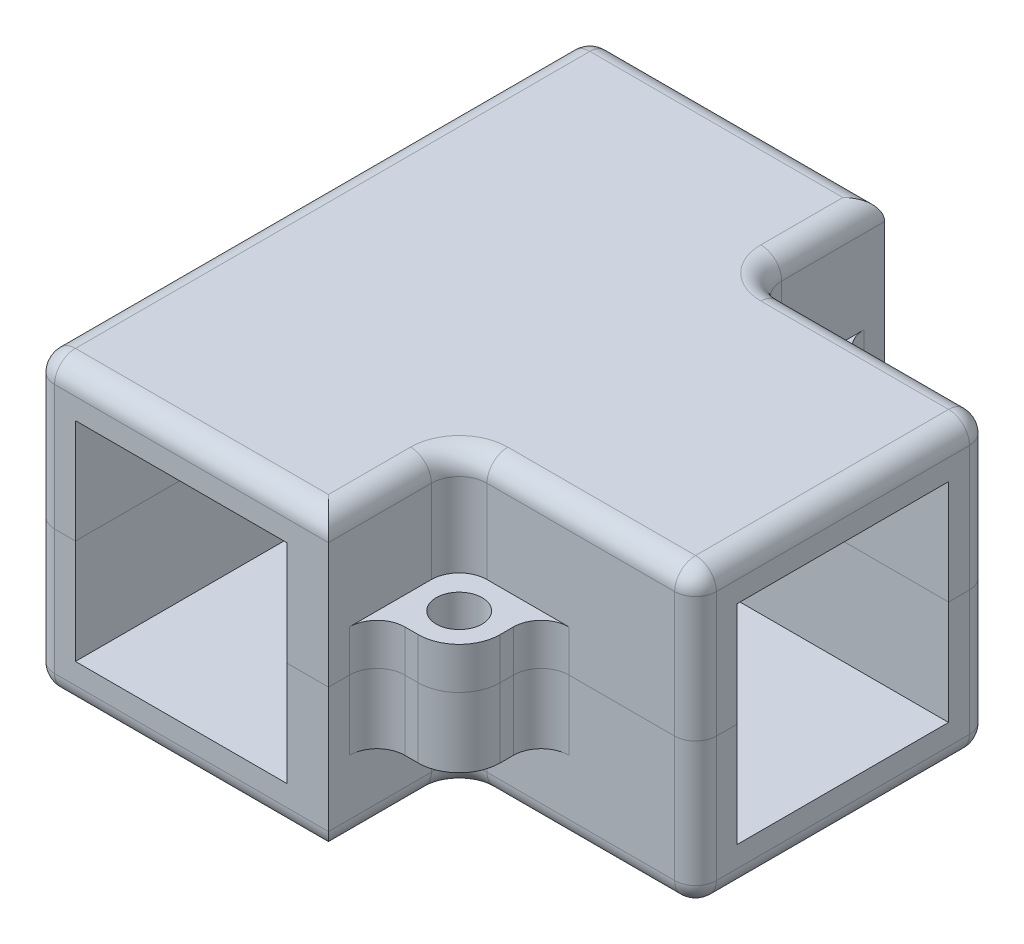
SolidWorks part; units mm, degrees
ref_plane "Front Plane" through (0, 0, 0) normal (0, 0, 1) x (1, 0, 0)
ref_plane "Top Plane" through (0, 0, 0) normal (0, 1, 0) x (1, 0, 0)
ref_plane "Right Plane" through (0, 0, 0) normal (1, 0, 0) x (0, 0, -1)
sketch "Sketch1" plane through (0, 0, 0) normal (0, 1, 0) x (1, 0, 0)
  line L0 (15.2, 20) -> (35.2, 20) construction
  line L1 (0, 0) -> (15.2, 0)
  line L2 (0, 0) -> (0, 40)
  line L3 (0, 40) -> (15.2, 40)
  line L4 (15.2, 0) -> (15.2, 40)
  line L6 (15.2, 12.4) -> (35.2, 12.4)
  line L7 (15.2, 12.4) -> (15.2, 27.6)
  line L8 (15.2, 27.6) -> (35.2, 27.6)
  line L9 (35.2, 12.4) -> (35.2, 27.6)
  line L10 (15.2, 12.4) -> (35.2, 27.6) construction
  line L11 (15.2, 27.6) -> (35.2, 12.4) construction
  point P7 (25.2, 20)
  dimension "D1" = 15.2
  dimension "D2" = 15.2
  dimension "D3" = 40
  dimension "D4" = 20
sketch "Sketch3" plane through (0, 0, 0) normal (0, 1, 0) x (1, 0, 0)
  line L0 (35.2, 27.6) -> (15.2, 27.6)
  line L1 (15.2, 27.6) -> (15.2, 40)
  line L2 (15.2, 40) -> (18.2, 40)
  line L3 (18.2, 40) -> (18.2, 30.6)
  line L4 (18.2, 30.6) -> (35.2, 30.6)
  line L5 (35.2, 30.6) -> (35.2, 27.6)
  line L6 (0, 20) -> (35.2, 20) construction
  line L7 (0, 0) -> (0, 40) construction
  line L8 (18.2, 9.4) -> (35.2, 9.4)
  line L9 (18.2, 0) -> (18.2, 9.4)
  line L10 (15.2, 0) -> (18.2, 0)
  line L11 (15.2, 12.4) -> (15.2, 0)
  line L12 (35.2, 12.4) -> (15.2, 12.4)
  line L13 (35.2, 9.4) -> (35.2, 12.4)
  line L15 (0, 40) -> (-3, 40)
  line L16 (0, 40) -> (0, 0)
  line L17 (0, 0) -> (-3, 0)
  line L18 (-3, 40) -> (-3, 0)
  dimension "D1" = 3
extrude "Boss-Extrude1" add sketch "Sketch3" along normal blind 7.5
sketch "Sketch4" plane through (0, 7.5, 0) normal (0, 1, 0) x (1, 0, 0)
  line L0 (-3, 40) -> (-3, 0)
  line L1 (-3, 0) -> (18.2, 0)
  line L2 (18.2, 0) -> (18.2, 9.4)
  line L3 (18.2, 9.4) -> (35.2, 9.4)
  line L4 (35.2, 9.4) -> (35.2, 30.6)
  line L5 (35.2, 30.6) -> (18.2, 30.6)
  line L6 (18.2, 30.6) -> (18.2, 40)
  line L7 (18.2, 40) -> (-3, 40)
extrude "Boss-Extrude2" add sketch "Sketch4" along normal blind 3
sketch "Sketch5" plane through (0, 0, 0) normal (0, 1, 0) x (1, 0, 0)
  line L0 (18.2, 30.6) -> (18.2, 40) construction
  line L1 (35.2, 30.6) -> (18.2, 30.6) construction
  line L4 (21.15, 36.5) -> (18.2, 36.5)
  line L5 (18.2, 36.5) -> (18.2, 30.6)
  line L6 (18.2, 30.6) -> (24.1, 30.6)
  line L7 (24.1, 30.6) -> (24.1, 33.55)
  line L8 (35.2, 20) -> (-3, 20) construction
  line L9 (35.2, 9.4) -> (35.2, 30.6) construction
  line L10 (-3, 40) -> (-3, 0) construction
  line L11 (24.1, 9.4) -> (24.1, 6.45)
  line L12 (18.2, 9.4) -> (24.1, 9.4)
  line L13 (18.2, 3.5) -> (18.2, 9.4)
  line L14 (21.15, 3.5) -> (18.2, 3.5)
  line L15 (-5.95, 22.95) -> (-3, 22.95)
  line L16 (-3, 22.95) -> (-3, 17.05)
  line L17 (-3, 17.05) -> (-5.95, 17.05)
  circle A0 centre (21.15, 33.55) radius 1.65
  circle A2 centre (21.15, 33.55) radius 2.95 construction
  arc A4 (24.1, 33.55) -> (21.15, 36.5) centre (21.15, 33.55) ccw
  circle A5 centre (21.15, 6.45) radius 2.95 construction
  arc A6 (24.1, 6.45) -> (21.15, 3.5) centre (21.15, 6.45) cw
  circle A7 centre (21.15, 6.45) radius 1.65
  circle A8 centre (-5.95, 20) radius 2.95 construction
  circle A9 centre (-5.95, 20) radius 1.65
  arc A10 (-5.95, 17.05) -> (-5.95, 22.95) centre (-5.95, 20) cw
  dimension "D1" = 3.3
  dimension "D2" = 5.9
  dimension "D3" = 5.9
  dimension "D4" = 3.3
extrude "Boss-Extrude3" add sketch "Sketch5" along normal blind 3
fillet "Fillet1" radius 2 2 edges at (18.2, 6.75, -9.4) (18.2, 6.75, -30.6)
fillet "Fillet2" radius 2 6 edges at (18.2, 1.5, -3.5) (24.1, 1.5, -9.4) (24.1, 1.5, -30.6) (18.2, 1.5, -36.5) (-3, 1.5, -22.95) (-3, 1.5, -17.05)
fillet "Fillet3" radius 1.5 14 edges at (18.2, 10.5, -36.3) (18.7858, 10.5, -31.1858) (27.7, 10.5, -30.6) (35.2, 10.5, -20) (27.7, 10.5, -9.4) (18.7858, 10.5, -8.8142) (18.2, 10.5, -3.7) (7.6, 10.5, 0) (-3, 10.5, -20) (7.6, 10.5, -40) (-3, 5.25, -40) (-3, 5.25, 0) (35.2, 5.25, -30.6) (35.2, 5.25, -9.4)
mirror "Mirror1" about plane through (0, 0, 0) normal (0, -1, 0) of bodies 105
sketch "Sketch6" plane through (0, 0, 0) normal (0, 1, 0) x (1, 0, 0)
  circle A0 centre (21.15, 6.45) radius 1.65 construction
  circle A1 centre (21.15, 33.55) radius 1.65 construction
  circle A2 centre (-5.95, 20) radius 1.65 construction
  circle A3 centre (21.15, 6.45) radius 1.65
  circle A4 centre (21.15, 33.55) radius 1.65
  circle A5 centre (-5.95, 20) radius 1.65
extrude "Boss-Extrude4" add sketch "Sketch6" against normal up to vertex (3 mm away) up to point (21.15, -3, -3.5)
other "Move Face1" face at (21.4523, -3, -33.8523) face at (21.4523, -3, -6.1477) face at (-5.0036, -3, -20) offset 2 parameters "D1"=2
sketch "Sketch7" plane through (0, 0, 0) normal (0, 1, 0) x (1, 0, 0)
  circle A0 centre (-5.95, 20) radius 2.1
  circle A1 centre (21.15, 33.55) radius 2.1
  circle A2 centre (21.15, 6.45) radius 2.1
  dimension "D1" = 4.2
extrude "Cut-Extrude1" cut sketch "Sketch7" against normal blind 3
